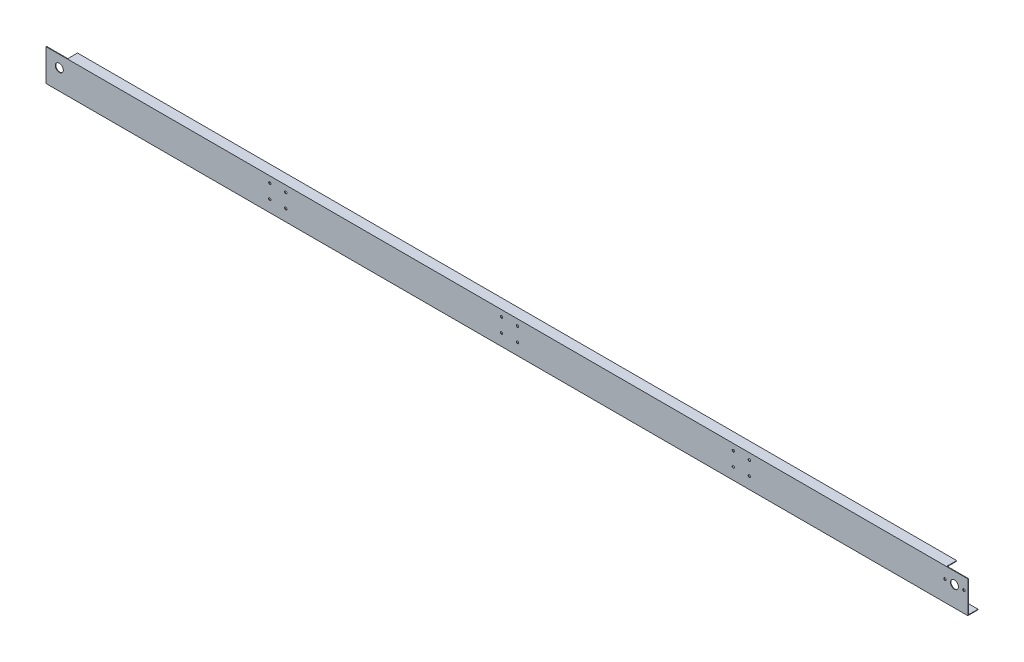
SolidWorks part; units mm, degrees
material "Galvanized Steel"
ref_plane "Front Plane" through (0, 0, 0) normal (0, 0, 1) x (1, 0, 0)
ref_plane "Top Plane" through (0, 0, 0) normal (0, 1, 0) x (1, 0, 0)
ref_plane "Right Plane" through (0, 0, 0) normal (1, 0, 0) x (0, 0, -1)
sketch "Sketch1" plane through (0, 0, 0) normal (1, 0, 0) x (0, 0, -1)
  line L0 (0, 0) -> (0, 127)
  line L1 (0, 127) -> (48.768, 127)
  line L4 (2.54, 1.6146) -> (2.54, 124.46)
  line L5 (2.54, 124.46) -> (48.768, 124.46)
  line L6 (48.768, 127) -> (48.768, 124.46)
  line L8 (0, 0) -> (0, -25.4)
  line L9 (0, -25.4) -> (48.768, -25.4)
  line L10 (48.768, -25.4) -> (48.768, -22.86)
  line L11 (48.768, -22.86) -> (2.54, -22.86)
  line L12 (0, 0) -> (48.768, -22.86) construction
  line L13 (2.54, 1.6146) -> (49.8461, -20.5601) construction
  line L14 (2.54, -22.86) -> (2.54, 1.6146)
  dimension "D1" = 127
  dimension "D2" = 48.768
  dimension "D4" = 48.768
  dimension "D3" = 25.4
  dimension "D5" = 2.54
  dimension "D6" = 2.54
extrude "Boss-Extrude1" add sketch "Sketch1" along normal blind 4394.2
sketch "Sketch2" plane through (0, 0, -2.54) normal (0, 0, -1) x (-1, 0, 0)
  line L0 (-4394.2, 127) -> (0, 127) construction
  line L1 (-4394.2, -22.86) -> (-4394.2, 124.46) construction
  line L2 (0, -22.86) -> (0, 124.46) construction
  circle A0 centre (-4330.7, 71.12) radius 19.05
  circle A1 centre (-63.5, 71.12) radius 19.05
  circle A2 centre (-4285.6547, 71.12) radius 5.5562
  circle A3 centre (-4375.7453, 71.12) radius 5.5562
  dimension "D1" = 38.1
  dimension "D4" = 38.1
  dimension "D7" = 11.1125
  dimension "D8" = 45.0453
  dimension "D2" = 55.88
  dimension "D3" = 63.5
  dimension "D5" = 55.88
  dimension "D6" = 63.5
  dimension "D9" = 45.0453
extrude "Cut-Extrude1" cut sketch "Sketch2" against normal up to next
sketch "Sketch3" plane through (0, 0, -2.54) normal (0, 0, -1) x (-1, 0, 0)
  line L19 (-4394.2, 124.46) -> (0, 124.46) construction
  line L20 (-4394.2, 127) -> (-4292.6, 127)
  line L21 (-4394.2, 127) -> (-4394.2, 124.46)
  line L22 (-4394.2, 124.46) -> (-4292.6, 124.46)
  line L23 (-4292.6, 127) -> (-4292.6, 124.46)
  line L25 (0, 127) -> (-101.6, 127)
  line L26 (0, 127) -> (0, 124.46)
  line L27 (0, 124.46) -> (-101.6, 124.46)
  line L28 (-101.6, 127) -> (-101.6, 124.46)
  dimension "D1" = 101.6
  dimension "D2" = 101.6
extrude "Cut-Extrude4" cut sketch "Sketch3" along normal up to next
sketch "Sketch4" plane through (0, 0, -2.54) normal (0, 0, -1) x (-1, 0, 0)
  circle A0 centre (-1066.8, 96.774) radius 5.5562
  circle A1 centre (-1066.8, 30.226) radius 5.5562
  circle A2 centre (-1143, 30.226) radius 5.5562
  circle A3 centre (-1143, 96.774) radius 5.5562
  circle A4 centre (-2171.7, 96.774) radius 5.5562
  circle A5 centre (-2171.7, 30.226) radius 5.5562
  circle A6 centre (-2247.9, 30.226) radius 5.5562
  circle A7 centre (-2247.9, 96.774) radius 5.5562
  circle A8 centre (-3276.6, 96.774) radius 5.5562
  circle A9 centre (-3276.6, 30.226) radius 5.5562
  circle A10 centre (-3352.8, 30.226) radius 5.5562
  circle A11 centre (-3352.8, 96.774) radius 5.5562
  circle A12 centre (-63.5, 71.12) radius 19.05 construction
  dimension "D3" = 11.1125
  dimension "D2" = 76.2
  dimension "D4" = 66.548
  dimension "D1" = 1003.3
  dimension "D6" = 3
extrude "Cut-Extrude5" cut sketch "Sketch4" against normal up to next
